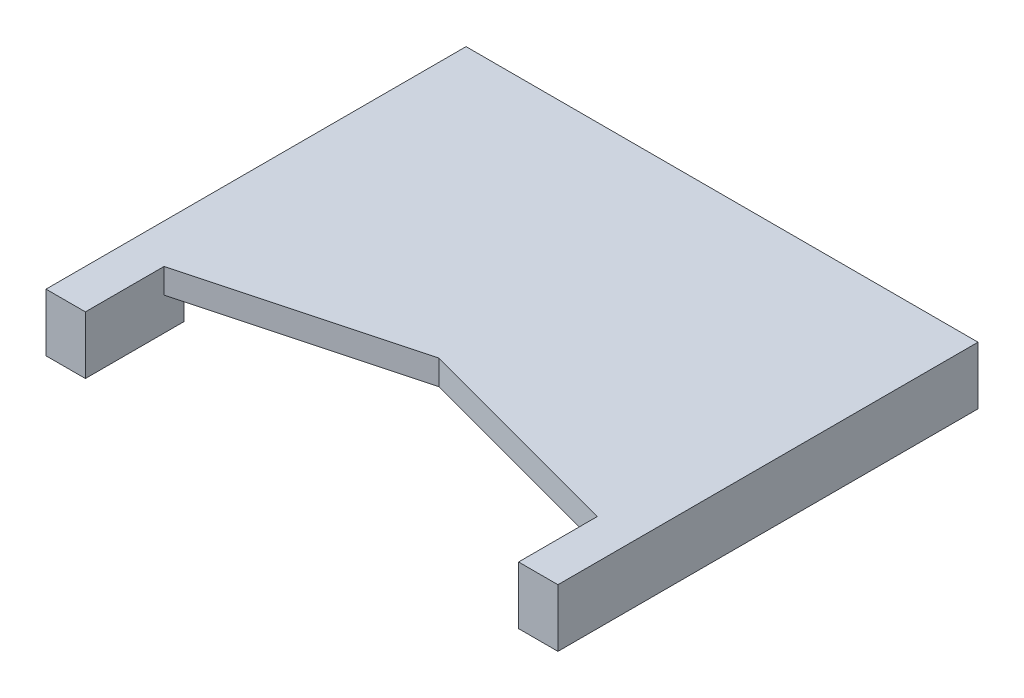
SolidWorks part; units mm, degrees
ref_plane "Front Plane" through (0, 0, 0) normal (0, 0, 1) x (1, 0, 0)
ref_plane "Top Plane" through (0, 0, 0) normal (0, 1, 0) x (1, 0, 0)
ref_plane "Right Plane" through (0, 0, 0) normal (1, 0, 0) x (0, 0, -1)
sketch "Sketch1" plane through (0, 0, 0) normal (0, 1, 0) x (1, 0, 0)
  line L1 (0, 0) -> (78, 0)
  line L2 (0, 0) -> (0, 64)
  line L3 (0, 64) -> (78, 64)
  line L4 (78, 0) -> (78, 64)
  dimension "D1" = 64
  dimension "D2" = 78
extrude "Boss-Extrude1" add sketch "Sketch1" along normal blind 8.8
sketch "Sketch2" plane through (0, 0, 0) normal (0, -1, 0) x (1, 0, 0)
  line L0 (78, -64) -> (0, -64) construction
  line L1 (3, -64) -> (75, -64)
  line L2 (3, -64) -> (3, -15)
  line L3 (3, -15) -> (75, -15)
  line L4 (75, -64) -> (75, -15)
  line L5 (0, -64) -> (0, 0) construction
  line L6 (78, 0) -> (78, -64) construction
  line L7 (0, 0) -> (78, 0) construction
  dimension "D1" = 3
  dimension "D2" = 3
  dimension "D3" = 15
extrude "Cut-Extrude1" cut sketch "Sketch2" against normal blind 5
sketch "Sketch3" plane through (0, 0, 0) normal (0, -1, 0) x (1, 0, 0)
  line L0 (75, -15) -> (3, -15) construction
  line L1 (6, -15) -> (72, -15)
  line L2 (6, -15) -> (6, 0)
  line L3 (6, 0) -> (72, 0)
  line L4 (72, -15) -> (72, 0)
  line L5 (0, 0) -> (78, 0) construction
  line L6 (0, -64) -> (0, 0) construction
  line L7 (78, 0) -> (78, -64) construction
  dimension "D1" = 6
  dimension "D2" = 6
extrude "Cut-Extrude2" cut sketch "Sketch3" against normal up to surface (5 mm away) up to face at (39, 5, -39.5)
sketch "Sketch4" plane through (0, 8.8, 0) normal (0, 1, 0) x (1, 0, 0)
  line L0 (6, 0) -> (6, 12)
  line L1 (6, 12) -> (39, 20.8423)
  line L2 (39, 20.8423) -> (72, 12)
  line L3 (72, 12) -> (72, 0)
  line L4 (72, 0) -> (6, 0)
  dimension "D1" = 150
  dimension "D2" = 12
extrude "Cut-Extrude3" cut sketch "Sketch4" against normal up to next
